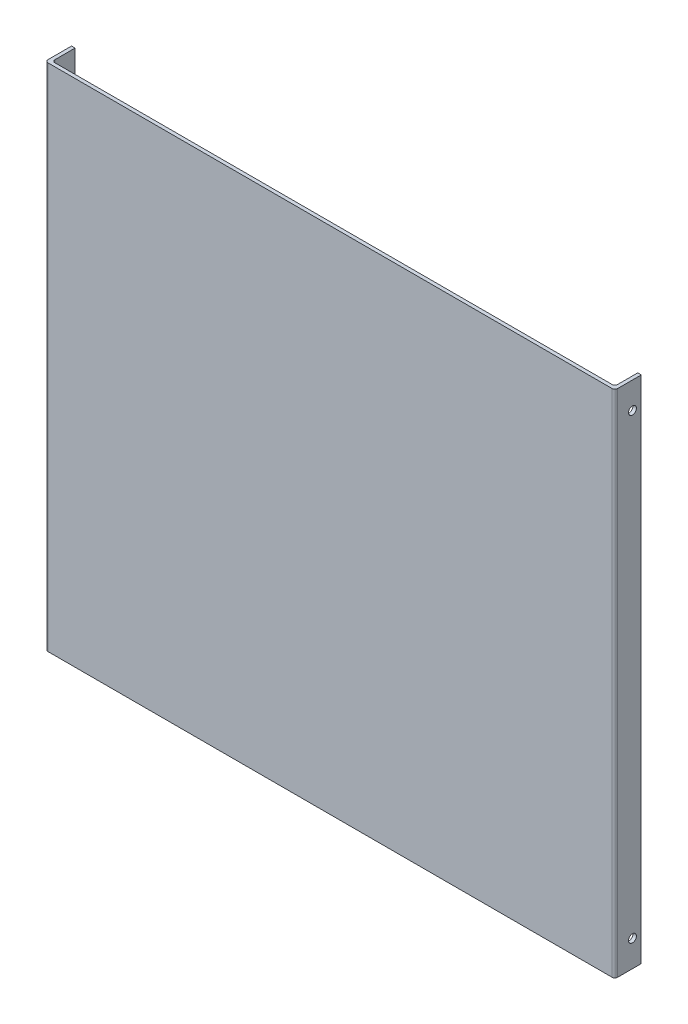
SolidWorks part; units mm, degrees
ref_plane "Plan de face" through (0, 0, 0) normal (0, 0, 1) x (1, 0, 0)
ref_plane "Plan de dessus" through (0, 0, 0) normal (0, 1, 0) x (1, 0, 0)
ref_plane "Plan de droite" through (0, 0, 0) normal (1, 0, 0) x (0, 0, -1)
sketch "Esquisse1" plane through (0, 0, 0) normal (0, 0, 1) x (1, 0, 0)
  line L1 (-160, -145) -> (160, -145)
  line L2 (-160, -145) -> (-160, 145)
  line L3 (-160, 145) -> (160, 145)
  line L4 (160, -145) -> (160, 145)
  line L5 (-160, -145) -> (160, 145) construction
  line L6 (-160, 145) -> (160, -145) construction
  point P0 (0, 0)
  dimension "D1" = 320
  dimension "D2" = 290
extrude "Boss.-Extru.1" add sketch "Esquisse1" along normal blind 2
sketch "Esquisse2" plane through (-160, 0, 0) normal (-1, 0, 0) x (0, 0, 1)
  line L0 (2, -145) -> (0, -145) construction
  line L1 (2, 145) -> (-13, 145)
  line L2 (2, 145) -> (2, -145)
  line L3 (2, -145) -> (-13, -145)
  line L4 (-13, 145) -> (-13, -145)
  dimension "D1" = 15
extrude "Boss.-Extru.2" add sketch "Esquisse2" along normal blind 2
fillet "Congé1" radius 1.5 2 edges at (-162, 0, 2)
mirror "Symétrie1" about plane through (0, 0, 0) normal (1, 0, 0) of "Congé1", "Boss.-Extru.2"
hole_wizard "Dégagement M41" positions "Esquisse4" profile "Esquisse3" hole size "M4" standard "Ansi Metric" end condition through all
sketch "Esquisse4" plane through (-162, 0, 0) normal (-1, 0, 0) x (0, 0, 1)
  line L2 (-13, 145) -> (-13, -145) construction
  line L3 (0.5, 0) -> (-31.0704, 0) construction
  line L4 (8.25, 0) -> (-8.25, 0) construction
  point P0 (-8, -130)
  point P29 (-8, 130)
  dimension "D1" = 130
  dimension "D2" = 5
sketch "Esquisse3" plane through (-162, -130, -8) normal (0, 1, 0) x (0, 0, 1)
  line L0 (0, 0) -> (0, 324)
  line L1 (0, 324) -> (2.25, 324)
  line L2 (2.25, 324) -> (2.25, 0)
  line L5 (2.25, 0) -> (0, 0)
  line L11 (0, -6.35) -> (0, 107.95) construction
  dimension "Diamètre du perçage jusqu'au prochain" = 4.5
  dimension "Profondeur du perçage jusqu'au prochain" = 324
